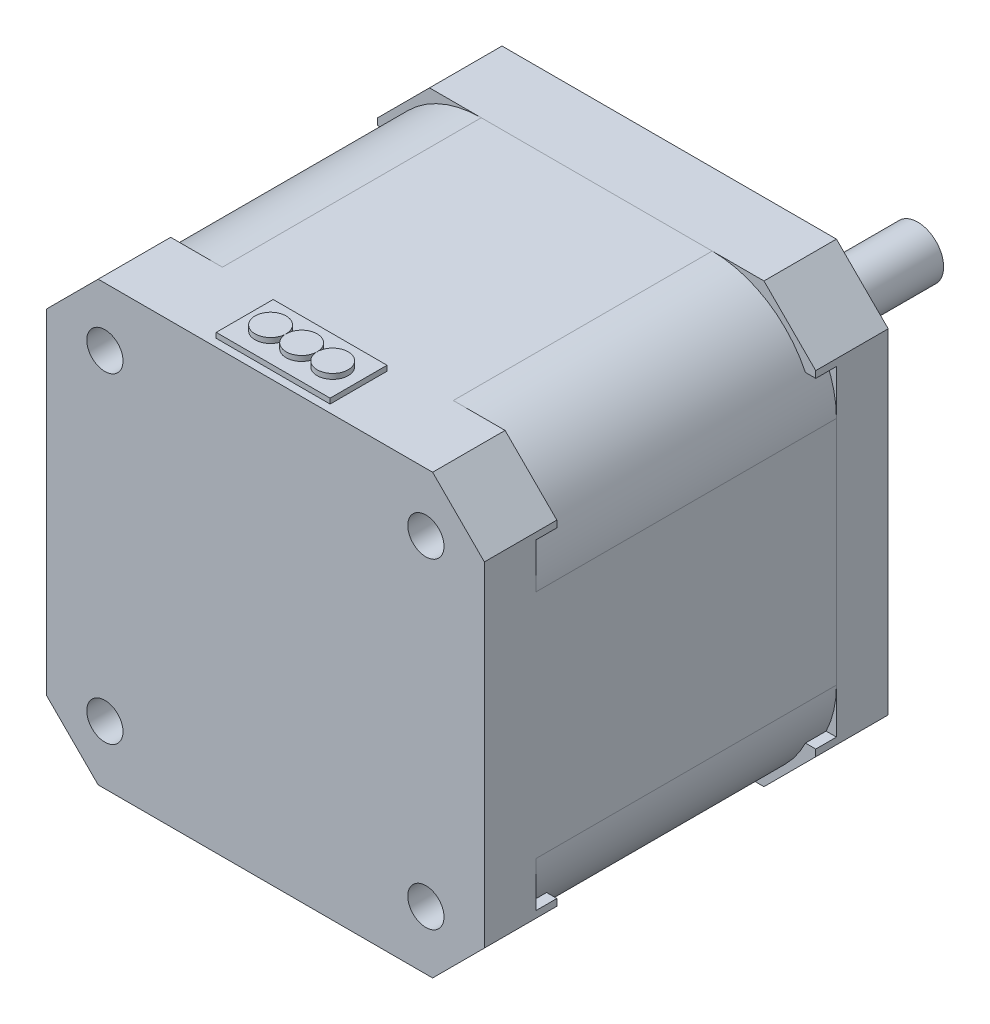
SolidWorks part; units mm, degrees
ref_plane "Plan de face" through (0, 0, 0) normal (0, 0, 1) x (1, 0, 0)
ref_plane "Plan de dessus" through (0, 0, 0) normal (0, 1, 0) x (1, 0, 0)
ref_plane "Plan de droite" through (0, 0, 0) normal (1, 0, 0) x (0, 0, -1)
sketch "Esquisse1" plane through (0, 0, 0) normal (0, 0, 1) x (1, 0, 0)
  line L1 (21.15, -21.15) -> (-21.15, -21.15)
  line L2 (21.15, -21.15) -> (21.15, 21.15)
  line L3 (21.15, 21.15) -> (-21.15, 21.15)
  line L4 (-21.15, -21.15) -> (-21.15, 21.15)
  line L5 (21.15, -21.15) -> (-21.15, 21.15) construction
  line L6 (21.15, 21.15) -> (-21.15, -21.15) construction
  line L7 (15.5, -15.5) -> (-15.5, -15.5) construction
  line L8 (15.5, -15.5) -> (15.5, 15.5) construction
  line L9 (15.5, 15.5) -> (-15.5, 15.5) construction
  line L10 (-15.5, -15.5) -> (-15.5, 15.5) construction
  line L11 (15.5, -15.5) -> (-15.5, 15.5) construction
  line L12 (15.5, 15.5) -> (-15.5, -15.5) construction
  circle A0 centre (-15.5, 15.5) radius 1.75
  circle A1 centre (15.5, 15.5) radius 1.75
  circle A2 centre (15.5, -15.5) radius 1.75
  circle A3 centre (-15.5, -15.5) radius 1.75
  circle A4 centre (0, 0) radius 2.5
  circle A5 centre (0, 0) radius 3.5
  circle A6 centre (0, 0) radius 11
  point P0 (0, 0)
  point P5 (0, 0)
  dimension "D3" = 3.5
  dimension "D4" = 5
  dimension "D6" = 22
  dimension "D1" = 42.3
  dimension "D2" = 31
  dimension "D5" = 1
extrude "Boss.-Extru.1" add sketch "Esquisse1" along normal blind 7 contours L4 L1 L2 L3 A6 A3 A2 A1 A0 | A6 A5 | A5 A4 | A4 region at (0, -20.5518, 0) region at (0, 0, 0) region at (-3.401, 0, 0) region at (-10.6889, 0, 0)
extrude "Boss.-Extru.2" add sketch "Esquisse1<3>" against normal blind 2 contours A6 A5 | A4 region at (0, 0, 0) region at (-10.6889, 0, 0)
sketch "Esquisse1<3>" plane through (0, 0, 0) normal (0, 0, 1) x (1, 0, 0) same geometry as "Esquisse1"
extrude "Boss.-Extru.3" add sketch "Esquisse1<5>" against normal blind 24 contours A4 region at (0, 0, 0)
sketch "Esquisse1<5>" plane through (0, 0, 0) normal (0, 0, 1) x (1, 0, 0) same geometry as "Esquisse1"
sketch "Esquisse2" plane through (-21.15, 0, 0) normal (-1, 0, 0) x (0, 0, 1)
  line L1 (5, 15.5) -> (7, 15.5)
  line L2 (5, 15.5) -> (5, -15.5)
  line L3 (5, -15.5) -> (7, -15.5)
  line L4 (7, 15.5) -> (7, -15.5)
  line L5 (5, 15.5) -> (7, -15.5) construction
  line L6 (5, -15.5) -> (7, 15.5) construction
  line L8 (7, -21.15) -> (7, 21.15) construction
  point P0 (6, 0)
  dimension "D1" = 2
  dimension "D2" = 31
extrude "Enlèv. mat.-Extru.1" cut sketch "Esquisse2" against normal up to next
sketch "Esquisse3" plane through (-21.15, 0, 0) normal (-1, 0, 0) x (0, 0, 1)
  line L0 (19.5, 0) -> (19.5, 21.15) construction
  line L1 (32, 21.15) -> (7, 21.15)
  line L2 (32, 21.15) -> (32, -21.15)
  line L3 (32, -21.15) -> (7, -21.15)
  line L4 (7, 21.15) -> (7, -21.15)
  line L5 (32, 21.15) -> (7, -21.15) construction
  line L6 (32, -21.15) -> (7, 21.15) construction
  line L7 (7, -15.5) -> (5, -15.5)
  line L8 (7, -15.5) -> (7, 15.5)
  line L9 (7, 15.5) -> (5, 15.5)
  line L10 (5, -15.5) -> (5, 15.5)
  line L11 (7, -15.5) -> (5, 15.5) construction
  line L12 (7, 15.5) -> (5, -15.5) construction
  line L13 (32, -15.5) -> (34, -15.5)
  line L14 (34, -15.5) -> (34, 15.5)
  line L15 (32, 15.5) -> (34, 15.5)
  point P0 (19.5, 0)
  point P6 (6, 0)
  line M8 (7, -15.5) -> (5, -15.5)
  line M9 (5, -15.5) -> (5, 15.5)
  line M10 (5, 15.5) -> (7, 15.5)
  line M11 (7, 15.5) -> (7, 21.15)
  line M15 (7, -21.15) -> (7, -15.5)
  dimension "D1" = 25
extrude "Boss.-Extru.4" add sketch "Esquisse3" against normal up to surface (42.3 mm away) separate body contours L4 L3 L2 L1 M11 M15 | L15 L2 L13 L14 | L4 M10 M9 M8 region at (-21.15, 0, 19.5) region at (-21.15, 0, 33) region at (-21.15, 0, 6) up to face at (21.15, 0, 4.75)
sketch "Esquisse4" plane through (-21.15, 0, 0) normal (-1, 0, 0) x (0, 0, 1)
  line L0 (32, 21.15) -> (39, 21.15)
  line L1 (39, 21.15) -> (39, -21.15)
  line L2 (39, -21.15) -> (32, -21.15)
  line L3 (7, 21.15) -> (0, 21.15) construction
  line L4 (32, 21.15) -> (32, 15.5)
  line L5 (32, 15.5) -> (34, 15.5)
  line L6 (34, 15.5) -> (34, -15.5)
  line L7 (34, -15.5) -> (32, -15.5)
  line L8 (32, -15.5) -> (32, -21.15)
extrude "Boss.-Extru.5" add sketch "Esquisse4" against normal up to surface (42.3 mm away) separate body up to face at (21.15, 0, 19.5)
extrude "Enlèv. mat.-Extru.2" cut sketch "Esquisse1<6>" along normal up to surface (39 mm away) contours A1 | A3 | A2 | A0 region at (-15.5, 15.5, 0) region at (15.5, 15.5, 0) region at (15.5, -15.5, 0) region at (-15.5, -15.5, 0) up to face at (0, 0, 39)
sketch "Esquisse1<6>" plane through (0, 0, 0) normal (0, 0, 1) x (1, 0, 0) same geometry as "Esquisse1"
chamfer "Chanfrein1" distance 5 angle 45 4 edges at (21.15, -21.15, 3.5) (21.15, 21.15, 3.5) (-21.15, 21.15, 3.5) (-21.15, -21.15, 3.5)
chamfer "Chanfrein2" distance 5 angle 45 4 edges at (-21.15, -21.15, 35.5) (21.15, -21.15, 35.5) (21.15, 21.15, 35.5) (-21.15, 21.15, 35.5)
fillet "Congé1" radius 10 4 edges at (-21.15, 21.15, 19.5) (-21.15, -21.15, 19.5) (21.15, -21.15, 19.5) (21.15, 21.15, 19.5)
sketch "Esquisse5" plane through (0, 21.15, 0) normal (0, 1, 0) x (1, 0, 0)
  line L1 (5.5, -32.75) -> (-5.5, -32.75)
  line L2 (5.5, -32.75) -> (5.5, -38.25)
  line L3 (5.5, -38.25) -> (-5.5, -38.25)
  line L4 (-5.5, -32.75) -> (-5.5, -38.25)
  line L5 (5.5, -32.75) -> (-5.5, -38.25) construction
  line L6 (5.5, -38.25) -> (-5.5, -32.75) construction
  line L7 (0, -39) -> (0, -32) construction
  line L8 (16.15, -32) -> (-16.15, -32) construction
  line L9 (16.15, -39) -> (-16.15, -39) construction
  circle A0 centre (-3, -35.5) radius 1.5
  circle A1 centre (0, -35.5) radius 1.5
  circle A2 centre (3, -35.5) radius 1.5
  point P0 (0, -35.5)
  point P18 (0, -35.5)
  dimension "D1" = 3
  dimension "D2" = 2.5
  dimension "D3" = 5.5
extrude "Boss.-Extru.6" add sketch "Esquisse5" along normal blind 0.5 contours L1 L4 L3 L2 A1 A2 A0 | A2 | A1 | A0 region at (5.377, 21.15, 35.5) region at (-3, 21.15, 35.5) region at (3, 21.15, 35.5) region at (0, 21.15, 35.5)
extrude "Boss.-Extru.7" add sketch "Esquisse5<3>" along normal blind 1 contours A0 region at (-3, 21.15, 35.5)
sketch "Esquisse5<3>" plane through (0, 21.15, 0) normal (0, 1, 0) x (1, 0, 0) same geometry as "Esquisse5"
extrude "Boss.-Extru.8" add sketch "Esquisse5<5>" along normal blind 1 contours A2 region at (3, 21.15, 35.5)
sketch "Esquisse5<5>" plane through (0, 21.15, 0) normal (0, 1, 0) x (1, 0, 0) same geometry as "Esquisse5"
extrude "Boss.-Extru.9" add sketch "Esquisse5<6>" along normal blind 1 separate body contours A1 region at (0, 21.15, 35.5)
sketch "Esquisse5<6>" plane through (0, 21.15, 0) normal (0, 1, 0) x (1, 0, 0) same geometry as "Esquisse5"
